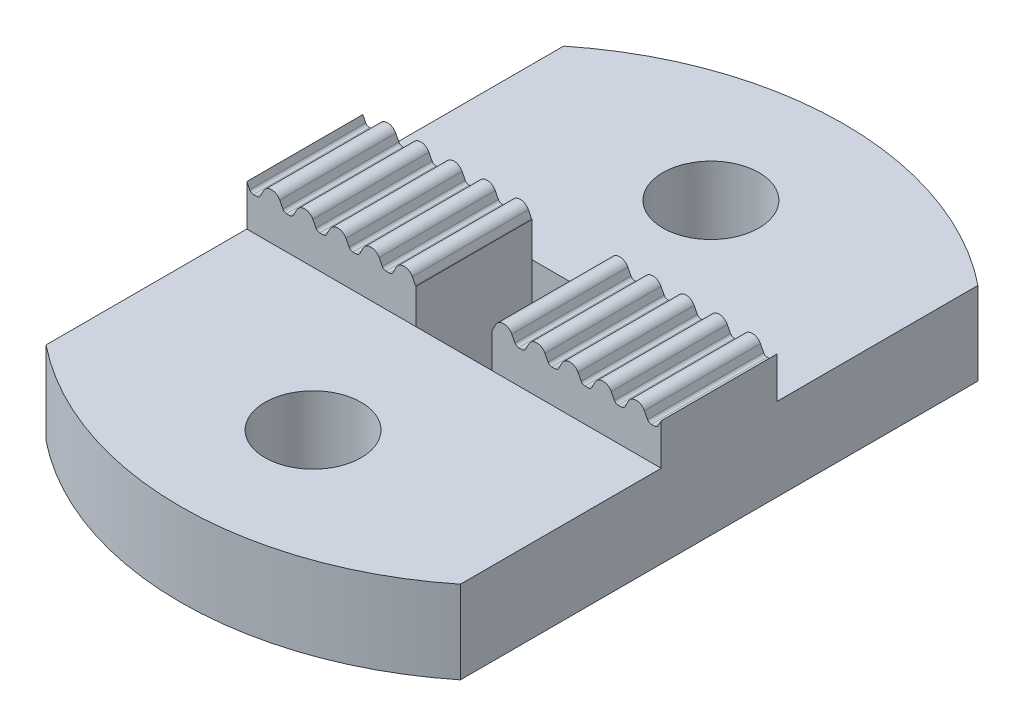
SolidWorks part; units mm, degrees
ref_plane "Front Plane" through (0, 0, 0) normal (0, 0, 1) x (1, 0, 0)
ref_plane "Top Plane" through (0, 0, 0) normal (0, 1, 0) x (1, 0, 0)
ref_plane "Right Plane" through (0, 0, 0) normal (1, 0, 0) x (0, 0, -1)
sketch "Sketch1" plane through (0, 0, 0) normal (0, 0, 1) x (1, 0, 0)
  line L0 (1.09, 0.25) -> (1.99, 0.25) construction
  line L1 (3.5789, 0.502) -> (3.7678, 0.1355)
  line L2 (3.99, 0) -> (4.18, 0)
  line L3 (1.5789, 0.502) -> (1.7678, 0.1355)
  line L4 (1.99, 0) -> (2.18, 0)
  line L5 (0.4122, 0.1355) -> (0.6011, 0.502)
  line L6 (1.09, 0.25) -> (0.19, 0.25) construction
  line L7 (0.19, 0) -> (0, 0)
  line L8 (2.4122, 0.1355) -> (2.6011, 0.502)
  line L9 (2.19, 0) -> (2, 0)
  line L10 (5.5789, 0.502) -> (5.7678, 0.1355)
  line L11 (5.99, 0) -> (6.18, 0)
  line L12 (4.4122, 0.1355) -> (4.6011, 0.502)
  line L13 (4.19, 0) -> (4, 0)
  line L14 (7.5789, 0.502) -> (7.7678, 0.1355)
  line L15 (7.99, 0) -> (8.18, 0)
  line L16 (6.4122, 0.1355) -> (6.6011, 0.502)
  line L17 (6.19, 0) -> (6, 0)
  line L18 (9.5789, 0.502) -> (9.7678, 0.1355)
  line L19 (9.99, 0) -> (10.18, 0)
  line L20 (8.4122, 0.1355) -> (8.6011, 0.502)
  line L21 (8.19, 0) -> (8, 0)
  line L22 (11.5789, 0.502) -> (11.7678, 0.1355)
  line L23 (11.99, 0) -> (12.18, 0)
  line L24 (10.4122, 0.1355) -> (10.6011, 0.502)
  line L25 (10.19, 0) -> (10, 0)
  line L26 (13.5789, 0.502) -> (13.7678, 0.1355)
  line L27 (13.99, 0) -> (14.18, 0)
  line L28 (12.4122, 0.1355) -> (12.6011, 0.502)
  line L29 (12.19, 0) -> (12, 0)
  line L30 (1.5789, 0.502) -> (3.5789, 0.502) construction
  line L31 (0, 0) -> (0, -5)
  line L32 (0, -5) -> (36.18, -5)
  line L33 (36.18, -5) -> (36.18, 0)
  line L34 (14.18, 0) -> (0, 0) construction
  line L35 (15.5789, 0.502) -> (15.7678, 0.1355)
  line L36 (15.99, 0) -> (16.18, 0)
  line L37 (14.4122, 0.1355) -> (14.6011, 0.502)
  line L38 (14.19, 0) -> (14, 0)
  line L39 (17.5789, 0.502) -> (17.7678, 0.1355)
  line L40 (17.99, 0) -> (18.18, 0)
  line L41 (16.4122, 0.1355) -> (16.6011, 0.502)
  line L42 (16.19, 0) -> (16, 0)
  line L43 (19.5789, 0.502) -> (19.7678, 0.1355)
  line L44 (19.99, 0) -> (20.18, 0)
  line L45 (18.4122, 0.1355) -> (18.6011, 0.502)
  line L46 (18.19, 0) -> (18, 0)
  line L47 (21.5789, 0.502) -> (21.7678, 0.1355)
  line L48 (21.99, 0) -> (22.18, 0)
  line L49 (20.4122, 0.1355) -> (20.6011, 0.502)
  line L50 (20.19, 0) -> (20, 0)
  line L51 (23.5789, 0.502) -> (23.7678, 0.1355)
  line L52 (23.99, 0) -> (24.18, 0)
  line L53 (22.4122, 0.1355) -> (22.6011, 0.502)
  line L54 (22.19, 0) -> (22, 0)
  line L55 (25.5789, 0.502) -> (25.7678, 0.1355)
  line L56 (25.99, 0) -> (26.18, 0)
  line L57 (24.4122, 0.1355) -> (24.6011, 0.502)
  line L58 (24.19, 0) -> (24, 0)
  line L59 (27.5789, 0.502) -> (27.7678, 0.1355)
  line L60 (27.99, 0) -> (28.18, 0)
  line L61 (26.4122, 0.1355) -> (26.6011, 0.502)
  line L62 (26.19, 0) -> (26, 0)
  line L63 (29.5789, 0.502) -> (29.7678, 0.1355)
  line L64 (29.99, 0) -> (30.18, 0)
  line L65 (28.4122, 0.1355) -> (28.6011, 0.502)
  line L66 (28.19, 0) -> (28, 0)
  line L67 (31.5789, 0.502) -> (31.7678, 0.1355)
  line L68 (31.99, 0) -> (32.18, 0)
  line L69 (30.4122, 0.1355) -> (30.6011, 0.502)
  line L70 (30.19, 0) -> (30, 0)
  line L71 (33.5789, 0.502) -> (33.7678, 0.1355)
  line L72 (33.99, 0) -> (34.18, 0)
  line L73 (32.4122, 0.1355) -> (32.6011, 0.502)
  line L74 (32.19, 0) -> (32, 0)
  line L75 (35.5789, 0.502) -> (35.7678, 0.1355)
  line L76 (35.99, 0) -> (36.18, 0)
  line L77 (34.4122, 0.1355) -> (34.6011, 0.502)
  line L78 (34.19, 0) -> (34, 0)
  arc A0 (1.5789, 0.502) -> (0.6011, 0.502) centre (1.09, 0.25) ccw
  arc A1 (1.7678, 0.1355) -> (1.99, 0) centre (1.99, 0.25) ccw
  arc A2 (0.19, 0) -> (0.4122, 0.1355) centre (0.19, 0.25) ccw
  arc A3 (3.5789, 0.502) -> (2.6011, 0.502) centre (3.09, 0.25) ccw
  arc A4 (3.7678, 0.1355) -> (3.99, 0) centre (3.99, 0.25) ccw
  arc A5 (2.19, 0) -> (2.4122, 0.1355) centre (2.19, 0.25) ccw
  arc A6 (5.5789, 0.502) -> (4.6011, 0.502) centre (5.09, 0.25) ccw
  arc A7 (5.7678, 0.1355) -> (5.99, 0) centre (5.99, 0.25) ccw
  arc A8 (4.19, 0) -> (4.4122, 0.1355) centre (4.19, 0.25) ccw
  arc A9 (7.5789, 0.502) -> (6.6011, 0.502) centre (7.09, 0.25) ccw
  arc A10 (7.7678, 0.1355) -> (7.99, 0) centre (7.99, 0.25) ccw
  arc A11 (6.19, 0) -> (6.4122, 0.1355) centre (6.19, 0.25) ccw
  arc A12 (9.5789, 0.502) -> (8.6011, 0.502) centre (9.09, 0.25) ccw
  arc A13 (9.7678, 0.1355) -> (9.99, 0) centre (9.99, 0.25) ccw
  arc A14 (8.19, 0) -> (8.4122, 0.1355) centre (8.19, 0.25) ccw
  arc A15 (11.5789, 0.502) -> (10.6011, 0.502) centre (11.09, 0.25) ccw
  arc A16 (11.7678, 0.1355) -> (11.99, 0) centre (11.99, 0.25) ccw
  arc A17 (10.19, 0) -> (10.4122, 0.1355) centre (10.19, 0.25) ccw
  arc A18 (13.5789, 0.502) -> (12.6011, 0.502) centre (13.09, 0.25) ccw
  arc A19 (13.7678, 0.1355) -> (13.99, 0) centre (13.99, 0.25) ccw
  arc A20 (12.19, 0) -> (12.4122, 0.1355) centre (12.19, 0.25) ccw
  arc A21 (15.5789, 0.502) -> (14.6011, 0.502) centre (15.09, 0.25) ccw
  arc A22 (15.7678, 0.1355) -> (15.99, 0) centre (15.99, 0.25) ccw
  arc A23 (14.19, 0) -> (14.4122, 0.1355) centre (14.19, 0.25) ccw
  arc A24 (17.5789, 0.502) -> (16.6011, 0.502) centre (17.09, 0.25) ccw
  arc A25 (17.7678, 0.1355) -> (17.99, 0) centre (17.99, 0.25) ccw
  arc A26 (16.19, 0) -> (16.4122, 0.1355) centre (16.19, 0.25) ccw
  arc A27 (19.5789, 0.502) -> (18.6011, 0.502) centre (19.09, 0.25) ccw
  arc A28 (19.7678, 0.1355) -> (19.99, 0) centre (19.99, 0.25) ccw
  arc A29 (18.19, 0) -> (18.4122, 0.1355) centre (18.19, 0.25) ccw
  arc A30 (21.5789, 0.502) -> (20.6011, 0.502) centre (21.09, 0.25) ccw
  arc A31 (21.7678, 0.1355) -> (21.99, 0) centre (21.99, 0.25) ccw
  arc A32 (20.19, 0) -> (20.4122, 0.1355) centre (20.19, 0.25) ccw
  arc A33 (23.5789, 0.502) -> (22.6011, 0.502) centre (23.09, 0.25) ccw
  arc A34 (23.7678, 0.1355) -> (23.99, 0) centre (23.99, 0.25) ccw
  arc A35 (22.19, 0) -> (22.4122, 0.1355) centre (22.19, 0.25) ccw
  arc A36 (25.5789, 0.502) -> (24.6011, 0.502) centre (25.09, 0.25) ccw
  arc A37 (25.7678, 0.1355) -> (25.99, 0) centre (25.99, 0.25) ccw
  arc A38 (24.19, 0) -> (24.4122, 0.1355) centre (24.19, 0.25) ccw
  arc A39 (27.5789, 0.502) -> (26.6011, 0.502) centre (27.09, 0.25) ccw
  arc A40 (27.7678, 0.1355) -> (27.99, 0) centre (27.99, 0.25) ccw
  arc A41 (26.19, 0) -> (26.4122, 0.1355) centre (26.19, 0.25) ccw
  arc A42 (29.5789, 0.502) -> (28.6011, 0.502) centre (29.09, 0.25) ccw
  arc A43 (29.7678, 0.1355) -> (29.99, 0) centre (29.99, 0.25) ccw
  arc A44 (28.19, 0) -> (28.4122, 0.1355) centre (28.19, 0.25) ccw
  arc A45 (31.5789, 0.502) -> (30.6011, 0.502) centre (31.09, 0.25) ccw
  arc A46 (31.7678, 0.1355) -> (31.99, 0) centre (31.99, 0.25) ccw
  arc A47 (30.19, 0) -> (30.4122, 0.1355) centre (30.19, 0.25) ccw
  arc A48 (33.5789, 0.502) -> (32.6011, 0.502) centre (33.09, 0.25) ccw
  arc A49 (33.7678, 0.1355) -> (33.99, 0) centre (33.99, 0.25) ccw
  arc A50 (32.19, 0) -> (32.4122, 0.1355) centre (32.19, 0.25) ccw
  arc A51 (35.5789, 0.502) -> (34.6011, 0.502) centre (35.09, 0.25) ccw
  arc A52 (35.7678, 0.1355) -> (35.99, 0) centre (35.99, 0.25) ccw
  arc A53 (34.19, 0) -> (34.4122, 0.1355) centre (34.19, 0.25) ccw
  dimension "D1" = 1.1
  dimension "D2" = 0.5
  dimension "D3" = 0.9
  dimension "D4" = 0.19
  dimension "D5" = 0.19
  dimension "D7" = 2
  dimension "D8" = 5
  dimension "D9" = 36.18
  dimension "D6" = 18
extrude "Boss-Extrude1" add sketch "Sketch1" along normal blind 7 contours A20 L29 L23 A16 L22 A15 L24 A17 L25 L19 A13 L18 A12 L20 A14 L21 L15 A10 L14 A9 L16 A11 L17 L11 A7 L10 A6 L12 A8 L13 L2 A4 L1 A3 L8 A5 L9 L4 A1 L3 A0 L5 A2 L7 L31 region at (18.09, -2.2826, 0)
sketch "Sketch2" plane through (0, 0, 0) normal (0, 1, 0) x (1, 0, 0)
  line L0 (0, -7) -> (36.18, 0) construction
  circle A0 centre (18.09, -3.5) radius 20
  dimension "D1" = 40
extrude "Boss-Extrude2" add sketch "Sketch2" against normal blind 5 from offset 2 offset against normal yes
sketch "Sketch4" plane through (0, -2, 0) normal (0, 1, 0) x (1, 0, 0)
  line L0 (0, 0) -> (36.18, 0)
  line L3 (15.79, 0) -> (20.39, 0)
  line L4 (15.79, 0) -> (15.79, -7)
  line L5 (15.79, -7) -> (20.39, -7)
  line L6 (20.39, 0) -> (20.39, -7)
  point P4 (18.09, 0)
  line M6 (36.18, -7) -> (0, -7)
  dimension "D1" = 7
  dimension "D2" = 4.6
extrude "Cut-Extrude2" cut sketch "Sketch4" against normal through all both and the other way through all contours L6 L0 L4 M6 region at (18.09, -2, 3.5)
sketch "Sketch5" plane through (0, -7, 0) normal (0, -1, 0) x (1, 0, 0)
  line L0 (18.09, 3.5) -> (18.09, 15.5) construction
  line L3 (18.09, 3.5) -> (18.09, -8.5) construction
  dimension "D1" = 12
hole_wizard "M5 Clearance Hole1" positions "3DSketch1" profile "Sketch6" hole size "M5" standard "ANSI Metric" end condition through all
sketch3d "3DSketch1"
  point P0 (18.09, -7, 15.5)
  point P3 (18.09, -7, -8.5)
sketch "Sketch6" plane through (18.09, -7, 15.5) normal (1, 0, 0) x (0, 0, -1)
  line L0 (0, 0) -> (0, 7.8)
  line L1 (0, 7.8) -> (2.9, 7.8)
  line L2 (2.9, 7.8) -> (2.9, 0)
  line L5 (2.9, 0) -> (0, 0)
  line L11 (0, -6.35) -> (0, 107.95) construction
  dimension "Thru Hole Dia." = 5.8
  dimension "Thru Hole Depth" = 7.8
sketch "Sketch7" plane through (0, -7, 0) normal (0, -1, 0) x (1, 0, 0)
  line L0 (18.09, 7) -> (18.09, 23.5) construction
  line L1 (5.59, 23.5) -> (30.59, 23.5)
  line L2 (5.59, 23.5) -> (5.59, -16.5)
  line L3 (5.59, -16.5) -> (30.59, -16.5)
  line L4 (30.59, 23.5) -> (30.59, -16.5)
  line L5 (20.39, 7) -> (15.79, 7) construction
  circle A0 centre (18.09, 3.5) radius 20 construction
  point P8 (0, 0)
  dimension "D1" = 25
extrude "Cut-Extrude3" cut sketch "Sketch7" against normal through all flip side to cut
